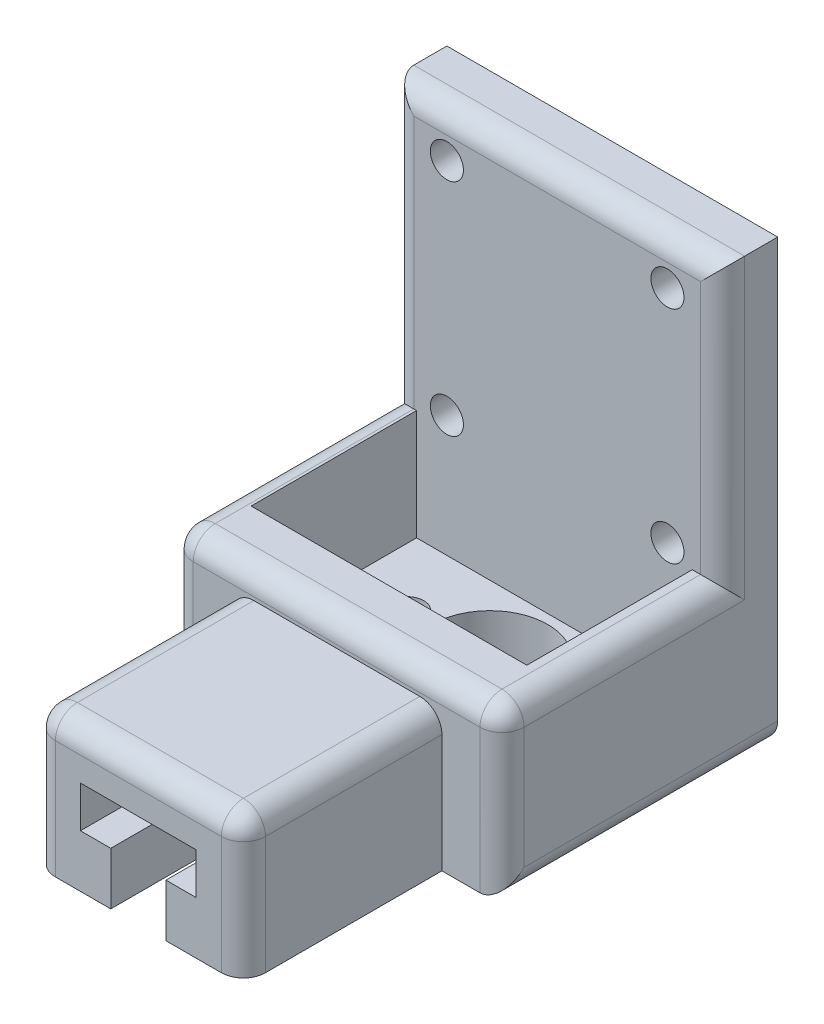
SolidWorks part; units mm, degrees
ref_plane "Front Plane" through (0, 0, 0) normal (0, 0, 1) x (1, 0, 0)
ref_plane "Top Plane" through (0, 0, 0) normal (0, 1, 0) x (1, 0, 0)
ref_plane "Right Plane" through (0, 0, 0) normal (1, 0, 0) x (0, 0, -1)
sketch "Sketch1" plane through (0, 0, 0) normal (0, 0, 1) x (1, 0, 0)
  line L1 (0, 0) -> (30, 0)
  line L2 (0, 0) -> (0, 15)
  line L3 (0, 15) -> (30, 15)
  line L4 (30, 0) -> (30, 15)
  dimension "D1" = 15
  dimension "D2" = 30
extrude "Boss-Extrude1" add sketch "Sketch1" along normal blind 20
sketch "Sketch2" plane through (0, 0, 0) normal (0, 0, -1) x (-1, 0, 0)
  line L0 (0, 0) -> (-30, 0) construction
  line L1 (-27.25, 0) -> (-2.25, 0)
  line L2 (-27.25, 0) -> (-27.25, 15)
  line L3 (-27.25, 15) -> (-2.25, 15)
  line L4 (-2.25, 0) -> (-2.25, 15)
  line L5 (0, 15) -> (0, 0) construction
  line L6 (-30, 0) -> (-30, 15) construction
  dimension "D1" = 25
  dimension "D2" = 2.25
  dimension "D3" = 15
  dimension "D4" = 2.75
extrude "Cut-Extrude1" cut sketch "Sketch2" against normal blind 15
sketch "Sketch3" plane through (0, 0, 20) normal (0, 0, 1) x (1, 0, 0)
  line L0 (0, 0) -> (30, 0) construction
  line L1 (5.5, 0) -> (24.55, 0)
  line L2 (5.5, 0) -> (5.5, 12.7)
  line L3 (5.5, 12.7) -> (24.55, 12.7)
  line L4 (24.55, 0) -> (24.55, 12.7)
  line L5 (0, 15) -> (0, 0) construction
  dimension "D1" = 19.05
  dimension "D2" = 5.5
  dimension "D3" = 12.7
extrude "Boss-Extrude2" add sketch "Sketch3" along normal blind 18
sketch "Sketch4" plane through (0, 0, 38) normal (0, 0, 1) x (1, 0, 0)
  line L0 (12.525, 0) -> (12.525, 4.7625)
  line L1 (5.5, 0) -> (24.55, 0) construction
  line L2 (12.525, 4.7625) -> (9.775, 4.7625)
  line L3 (9.775, 4.7625) -> (9.775, 8.5125)
  line L4 (9.775, 8.5125) -> (20.275, 8.5125)
  line L5 (20.275, 8.5125) -> (20.275, 4.7625)
  line L6 (20.275, 4.7625) -> (17.525, 4.7625)
  line L7 (17.525, 4.7625) -> (17.525, 0)
  line L8 (17.525, 0) -> (12.525, 0)
  line L9 (5.5, 12.7) -> (5.5, 0) construction
  line L10 (24.55, 0) -> (24.55, 12.7) construction
  dimension "D1" = 10.5
  dimension "D2" = 3.75
  dimension "D3" = 2.75
  dimension "D4" = 2.75
  dimension "D5" = 4.7625
  dimension "D6" = 4.275
  dimension "D7" = 4.275
extrude "Cut-Extrude2" cut sketch "Sketch4" against normal blind 20
sketch "Sketch5" plane through (0, 0, 18) normal (0, 0, 1) x (1, 0, 0)
  line L1 (12.525, 0) -> (17.525, 0)
  line L2 (12.525, 0) -> (12.525, 4.7625)
  line L3 (12.525, 4.7625) -> (17.525, 4.7625)
  line L4 (17.525, 0) -> (17.525, 4.7625)
extrude "Boss-Extrude3" add sketch "Sketch5" along normal blind 3.175
sketch "Sketch6" [suppressed] plane through (0, 0, 0) normal (0, 0, -1) x (-1, 0, 0)
  line L0 (-30, 0) -> (-30, 15) construction
  line L1 (-30, 8) -> (-27.75, 8)
  line L2 (-30, 8) -> (-30, 0)
  line L3 (-30, 0) -> (-27.75, 0)
  line L4 (-27.75, 8) -> (-27.75, 0)
  line L5 (-2.25, 0) -> (-2.25, 12.5) construction
  line L6 (-2.25, 8) -> (0, 8)
  line L7 (-2.25, 8) -> (-2.25, 0)
  line L8 (-2.25, 0) -> (0, 0)
  line L9 (0, 8) -> (0, 0)
  dimension "D1" = 8
  dimension "D2" = 8
extrude "Boss-Extrude4" [suppressed] add sketch "Sketch6" along normal blind 5
sketch "Sketch7" plane through (0, 15, 0) normal (0, 1, 0) x (1, 0, 0)
  line L0 (30, 0) -> (27.25, 0) construction
  line L1 (26.125, 8) -> (31.125, 8)
  line L2 (26.125, 8) -> (26.125, -8)
  line L3 (26.125, -8) -> (31.125, -8)
  line L4 (31.125, 8) -> (31.125, -8)
  line L5 (26.125, 8) -> (31.125, -8) construction
  line L6 (26.125, -8) -> (31.125, 8) construction
  circle A0 centre (28.625, -8) radius 2.5
  point P0 (28.625, 0)
  line M3 (30, 0) -> (27.25, 0)
  dimension "D1" = 5
  dimension "D2" = 8
extrude "Cut-Extrude3" [suppressed] cut sketch "Sketch7" against normal blind 5 contours L3 A0 | L3 A0 | A0 L4 L2 M3
sketch "Sketch8" [suppressed] plane through (30, 0, 0) normal (1, 0, 0) x (0, 0, -1)
  line L0 (2.5, 8) -> (2.5, 0) construction
  line L1 (5, 8) -> (0, 8) construction
  line L2 (-20, 0) -> (5, 0) construction
  circle A0 centre (2.5, 4) radius 1.375
  point P6 (2.5, 4)
  dimension "D1" = 2.75
extrude "Cut-Extrude4" [suppressed] cut sketch "Sketch8" against normal through all
chamfer "Chamfer1" [suppressed] distance 3 angle 45
sketch "Sketch9" plane through (30, 0, 0) normal (-1, 0, 0) x (0, 0, 1)
  line L0 (15, 0) -> (-5, 0)
  line L1 (-5, 0) -> (-5, 40)
  line L3 (-5, 40) -> (0, 40)
  line L4 (0, 40) -> (0, 5)
  line L5 (0, 15) -> (0, 0) construction
  line L6 (0, 5) -> (15, 5)
  line L7 (15, 15) -> (15, 0) construction
  line L8 (15, 5) -> (15, 0)
  dimension "D1" = 20
  dimension "D2" = 40
  dimension "D3" = 35
extrude "Boss-Extrude12" add sketch "Sketch9" along normal up to surface (30 mm away) up to face at (0, 7.5, 10)
sketch "Sketch10" plane through (0, 0, 0) normal (0, 0, 1) x (1, 0, 0)
  line L0 (0, 40) -> (0, 15) construction
  line L1 (5, 36) -> (25, 36)
  line L2 (5, 36) -> (5, 16)
  line L3 (5, 16) -> (25, 16)
  line L4 (25, 36) -> (25, 16)
  line L5 (0, 40) -> (30, 40) construction
  dimension "D1" = 20
  dimension "D2" = 20
  dimension "D3" = 5
  dimension "D4" = 4
hole_wizard "Ø2.5mm Dowel Hole1" positions "Sketch11" profile "Sketch12" hole size "Ø2.5" standard "ANSI Metric" end condition through all
sketch "Sketch11" plane through (0, 0, 0) normal (0, 0, 1) x (1, 0, 0)
  point P0 (5, 36)
  point P3 (25, 36)
  point P6 (5, 16)
  point P9 (25, 16)
sketch "Sketch12" plane through (5, 36, 0) normal (1, 0, 0) x (0, -1, 0)
  line L0 (0, 0) -> (0, 5)
  line L1 (0, 5) -> (1.5, 5)
  line L2 (1.5, 5) -> (1.5, 0)
  line L5 (1.5, 0) -> (0, 0)
  line L11 (0, -6.35) -> (0, 107.95) construction
  dimension "Thru Hole Dia." = 3
  dimension "Thru Hole Depth" = 5
sketch "Sketch13" plane through (0, 5, 0) normal (0, 1, 0) x (1, 0, 0)
  line L0 (0, 5) -> (30, 5) construction
  circle A0 centre (15, -6.1) radius 5.25
  circle A1 centre (22.5, -6.1) radius 1.5
  circle A2 centre (7.5, -6.1) radius 1.5
  point P8 (15, 5)
  dimension "D1" = 3
  dimension "D2" = 3
  dimension "D3" = 10.5
  dimension "D4" = 7.5
  dimension "D5" = 7.5
  dimension "D7" = 11.1
  dimension "D6" = 0
extrude "Cut-Extrude5" cut sketch "Sketch13" against normal through all
fillet "Fillet1" radius 2 15 edges at (0, 0, 7.5) (30, 0, 7.5) (15, 40, 0) (30, 27.5, 0) (0, 27.5, 0) (30, 15, 10) (0, 15, 10) (15, 15, 20) (0, 7.5, 20) (30, 7.5, 20) (5.5, 12.7, 29) (24.55, 12.7, 29) (5.5, 6.35, 38) (24.55, 6.35, 38) (15.025, 12.7, 38)
